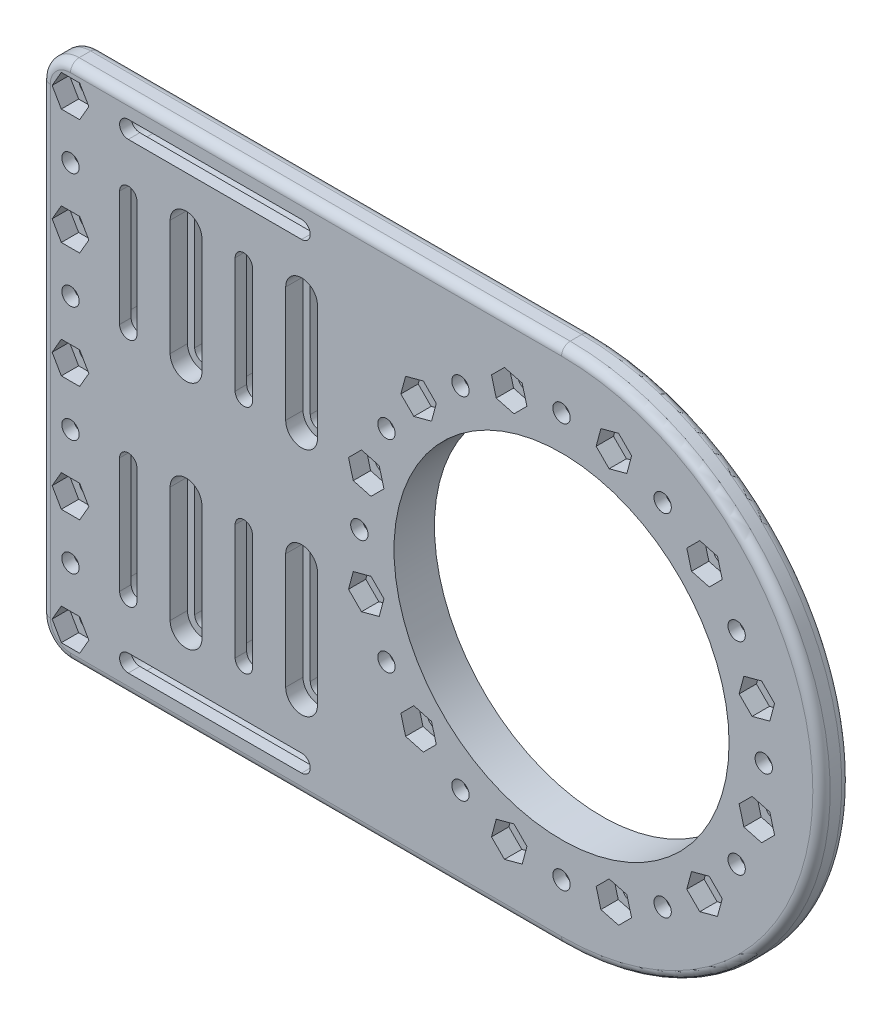
SolidWorks part; units mm, degrees
ref_plane "前视基准面" through (0, 0, 0) normal (0, 0, 1) x (1, 0, 0)
ref_plane "上视基准面" through (0, 0, 0) normal (0, 1, 0) x (1, 0, 0)
ref_plane "右视基准面" through (0, 0, 0) normal (1, 0, 0) x (0, 0, -1)
other "Configuration Table"
sketch "草图1" plane through (0, 0, 0) normal (0, 0, 1) x (1, 0, 0)
  line L1 (-45, -45) -> (45, -45)
  line L2 (-45, -45) -> (-45, 45)
  line L3 (-45, 45) -> (45, 45)
  line L4 (45, -45) -> (45, 45) construction
  line L5 (-45, -45) -> (45, 45) construction
  line L6 (-45, 45) -> (45, -45) construction
  arc A0 (45, -45) -> (45, 45) centre (45, 0) ccw
  point P0 (0, 0)
  dimension "D1" = 90
  dimension "D2" = 90
extrude "凸台-拉伸1" add sketch "草图1" along normal blind 5
sketch "草图2" plane through (0, 0, 5) normal (0, 0, 1) x (1, 0, 0)
  circle A0 centre (45, 0) radius 29
  dimension "D1" = 58
extrude "切除-拉伸1" cut sketch "草图2" against normal through all
sketch "草图3" plane through (0, 0, 0) normal (0, 0, 1) x (1, 0, 0)
  circle A0 centre (45, 0) radius 29
  circle A1 centre (45, 0) radius 45
  circle A2 centre (45, 0) radius 29 construction
  dimension "D1" = 90
extrude "凸台-拉伸2" add sketch "草图3" against normal blind 2
sketch "草图9" plane through (0, 0, -2) normal (0, 0, -1) x (-1, 0, 0)
  circle A0 centre (-45, 0) radius 45
  circle A1 centre (-45, 0) radius 31
  dimension "D1" = 62
extrude "切除-拉伸10" cut sketch "草图9" against normal blind 2
sketch "草图5" plane through (0, 0, 0) normal (0, 0, -1) x (-1, 0, 0)
  line L1 (-45, 35) -> (-45, 0) construction
  circle A0 centre (-45, 0) radius 35 construction
  circle A1 centre (-45, 35) radius 1.5
  dimension "D1" = 3
  dimension "D2" = 70
extrude "切除-拉伸2" cut sketch "草图5" against normal through all
sketch "草图6" plane through (0, 0, 0) normal (0, 0, -1) x (-1, 0, 0)
  line L0 (-45, 35) -> (-45, 0) construction
  line L1 (-45, 31.8246) -> (-42.25, 33.4123)
  line L2 (-42.25, 33.4123) -> (-42.25, 36.5877)
  line L3 (-42.25, 36.5877) -> (-45, 38.1754)
  line L4 (-45, 38.1754) -> (-47.75, 36.5877)
  line L5 (-47.75, 36.5877) -> (-47.75, 33.4123)
  line L6 (-47.75, 33.4123) -> (-45, 31.8246)
  circle A1 centre (-45, 35) radius 2.75 construction
  dimension "D1" = 5.5
extrude "切除-拉伸3" cut sketch "草图6" against normal blind 3
sketch "草图10" plane through (0, 0, -2) normal (0, 0, -1) x (-1, 0, 0)
  line L0 (-45, 0) -> (-35.9413, 33.8074) construction
  line L1 (-45, -1000) -> (-45, 49000) construction
  circle A0 centre (-35.9413, 33.8074) radius 1.5
  circle A1 centre (-45, 0) radius 35 construction
  dimension "D1" = 3
  dimension "D2" = 15
extrude "切除-拉伸11" cut sketch "草图10" against normal through all
sketch "草图11" plane through (0, 0, 5) normal (0, 0, 1) x (1, 0, 0)
  line L0 (35.9413, 33.8074) -> (45, 0) construction
  line L1 (36.7632, 30.7402) -> (39.0086, 32.9855)
  line L2 (39.0086, 32.9855) -> (38.1867, 36.0528)
  line L3 (38.1867, 36.0528) -> (35.1195, 36.8746)
  line L4 (35.1195, 36.8746) -> (32.8741, 34.6293)
  line L5 (32.8741, 34.6293) -> (33.696, 31.562)
  line L6 (33.696, 31.562) -> (36.7632, 30.7402)
  circle A0 centre (35.9413, 33.8074) radius 2.75 construction
  dimension "D1" = 5.5
extrude "切除-拉伸12" cut sketch "草图11" against normal blind 3
pattern_circular "阵列(圆周)1" count 12 over 360 about axis through (45, 0, 0) along (0, 0, 1) of "切除-拉伸3", "切除-拉伸2", "切除-拉伸11", "切除-拉伸12", "切除-拉伸1"
sketch "草图7" plane through (0, 0, 5) normal (0, 0, 1) x (1, 0, 0)
  line L0 (-30, 40) -> (0, 40) construction
  line L1 (-30, 41.5) -> (0, 41.5)
  line L2 (-30, 38.5) -> (0, 38.5)
  line L3 (-1000, 0) -> (49000, 0) construction
  line L4 (-30, -40) -> (0, -40) construction
  line L7 (-30, -41.5) -> (0, -41.5)
  line L8 (-30, -38.5) -> (0, -38.5)
  line L9 (-45, 45) -> (-45, -45) construction
  arc A0 (-30, 41.5) -> (-30, 38.5) centre (-30, 40) ccw
  arc A1 (0, 38.5) -> (0, 41.5) centre (0, 40) ccw
  arc A4 (-30, -41.5) -> (-30, -38.5) centre (-30, -40) cw
  arc A5 (0, -38.5) -> (0, -41.5) centre (0, -40) cw
  point P2 (-15, 40)
  point P12 (-15, -40)
  dimension "D1" = 3
  dimension "D2" = 80
  dimension "D3" = 15
  dimension "D4" = 30
sketch "草图8" plane through (0, 0, 0) normal (0, 0, 1) x (1, 0, 0)
  line L0 (-30, 40) -> (0, 40) construction
  line L1 (-30, 42.75) -> (0, 42.75)
  line L2 (-30, 37.25) -> (0, 37.25)
  line L3 (-30, -40) -> (0, -40) construction
  line L4 (-30, -37.25) -> (0, -37.25)
  line L5 (-30, -42.75) -> (0, -42.75)
  arc A0 (-30, 42.75) -> (-30, 37.25) centre (-30, 40) ccw
  arc A1 (0, 37.25) -> (0, 42.75) centre (0, 40) ccw
  arc A2 (-30, -37.25) -> (-30, -42.75) centre (-30, -40) ccw
  arc A3 (0, -42.75) -> (0, -37.25) centre (0, -40) ccw
  point P4 (-15, 40)
  point P13 (-15, -40)
  dimension "D1" = 5.5
  dimension "D2" = 5.5
extrude "切除-拉伸7" cut sketch "草图7" against normal through all
extrude "切除-拉伸9" cut sketch "草图8" along normal blind 3
sketch "草图12" plane through (0, 0, 5) normal (0, 0, 1) x (1, 0, 0)
  line L0 (-45, 45) -> (-45, -45) construction
  circle A0 centre (-40, 0) radius 1.5
  dimension "D2" = 3
  dimension "D1" = 5
sketch "草图13" plane through (0, 0, 5) normal (0, 0, 1) x (1, 0, 0)
  line L1 (-36.8246, 0) -> (-38.4123, 2.75)
  line L2 (-38.4123, 2.75) -> (-41.5877, 2.75)
  line L3 (-41.5877, 2.75) -> (-43.1754, 0)
  line L4 (-43.1754, 0) -> (-41.5877, -2.75)
  line L5 (-41.5877, -2.75) -> (-38.4123, -2.75)
  line L6 (-38.4123, -2.75) -> (-36.8246, 0)
  circle A1 centre (-40, 0) radius 2.75 construction
  dimension "D1" = 5.5
extrude "切除-拉伸13" cut sketch "草图12" against normal through all
extrude "切除-拉伸14" cut sketch "草图13" against normal blind 3
pattern_linear "阵列(线性)5" count 5 spacing 10 along (0, -1, 0) count 5 spacing 10 along (0, 1, 0) of "切除-拉伸13"
pattern_linear "阵列(线性)1" count 3 spacing 20 along (0, -1, 0) count 3 spacing 20 along (0, 1, 0) of "切除-拉伸14"
sketch "草图14" plane through (0, 0, 5) normal (0, 0, 1) x (1, 0, 0)
  line L0 (0, 30) -> (0, 10) construction
  line L1 (1.5, 30) -> (1.5, 10)
  line L2 (-1.5, 30) -> (-1.5, 10)
  line L3 (-1000, 0) -> (49000, 0) construction
  line L4 (0, -30) -> (0, -10) construction
  line L5 (1.5, -30) -> (1.5, -10)
  line L6 (-1.5, -30) -> (-1.5, -10)
  arc A0 (1.5, 30) -> (-1.5, 30) centre (0, 30) ccw
  arc A1 (-1.5, 10) -> (1.5, 10) centre (0, 10) ccw
  arc A2 (1.5, -30) -> (-1.5, -30) centre (0, -30) cw
  arc A3 (-1.5, -10) -> (1.5, -10) centre (0, -10) cw
  circle A4 centre (45, 0) radius 45 construction
  point P2 (0, 20)
  point P12 (0, -20)
  dimension "D1" = 3
  dimension "D2" = 30
  dimension "D3" = 20
  dimension "D4" = 0
sketch "草图15" plane through (0, 0, 5) normal (0, 0, 1) x (1, 0, 0)
  line L0 (0, 10) -> (0, 30) construction
  line L1 (-2.75, 10) -> (-2.75, 30)
  line L2 (2.75, 10) -> (2.75, 30)
  line L3 (0, -10) -> (0, -30) construction
  line L4 (2.75, -10) -> (2.75, -30)
  line L5 (-2.75, -10) -> (-2.75, -30)
  arc A0 (-2.75, 10) -> (2.75, 10) centre (0, 10) ccw
  arc A1 (2.75, 30) -> (-2.75, 30) centre (0, 30) ccw
  arc A2 (2.75, -10) -> (-2.75, -10) centre (0, -10) ccw
  arc A3 (-2.75, -30) -> (2.75, -30) centre (0, -30) ccw
  point P4 (0, 20)
  point P9 (0, -20)
  dimension "D1" = 5.5
  dimension "D2" = 5.5
sketch "草图17" plane through (0, 0, 0) normal (0, 0, -1) x (-1, 0, 0)
  line L1 (43.1754, 10) -> (41.5877, 12.75)
  line L2 (41.5877, 12.75) -> (38.4123, 12.75)
  line L3 (38.4123, 12.75) -> (36.8246, 10)
  line L4 (36.8246, 10) -> (38.4123, 7.25)
  line L5 (38.4123, 7.25) -> (41.5877, 7.25)
  line L6 (41.5877, 7.25) -> (43.1754, 10)
  circle A0 centre (40, 10) radius 2.75 construction
  dimension "D1" = 5.5
extrude "切除-拉伸18" cut sketch "草图17" against normal blind 3
pattern_linear "阵列(线性)6" count 3 spacing 20 along (0, -1, 0) count 3 spacing 20 along (0, 1, 0) of "切除-拉伸18"
extrude "切除-拉伸15" cut sketch "草图14" against normal through all
extrude "切除-拉伸16" cut sketch "草图15" against normal blind 3
pattern_linear "阵列(线性)2" count 4 spacing 10 along (-1, 0, 0) of "切除-拉伸15"
pattern_linear "阵列(线性)3" count 2 spacing 20 along (-1, 0, 0) of "切除-拉伸16"
sketch "草图16" plane through (0, 0, 0) normal (0, 0, -1) x (-1, 0, 0)
  line L0 (30, 30) -> (30, 10) construction
  line L3 (32.75, 30) -> (32.75, 10)
  line L6 (27.25, 30) -> (27.25, 10)
  line L7 (30, -10) -> (30, -30) construction
  line L8 (32.75, -10) -> (32.75, -30)
  line L9 (27.25, -10) -> (27.25, -30)
  arc A4 (32.75, 30) -> (27.25, 30) centre (30, 30) ccw
  arc A5 (27.25, 10) -> (32.75, 10) centre (30, 10) ccw
  arc A6 (32.75, -10) -> (27.25, -10) centre (30, -10) ccw
  arc A7 (27.25, -30) -> (32.75, -30) centre (30, -30) ccw
  point P4 (30, 20)
  point P9 (30, -20)
  dimension "D1" = 5.5
  dimension "D2" = 5.5
extrude "切除-拉伸17" cut sketch "草图16" against normal blind 3
pattern_linear "阵列(线性)4" count 2 spacing 20 along (1, 0, 0) of "切除-拉伸17"
fillet "圆角4" radius 1.5 8 edges at (0, -45, 5) (0, -45, 0) (90, 0, 0) (0, 45, 5) (0, 45, 0) (90, 0, 5) (-45, 0, 5) (-45, 0, 0)
fillet "圆角5" radius 5 6 edges at (-44.5607, -44.5607, 0.4393) (-44.5607, -44.5607, 4.5607) (-44.5607, 44.5607, 0.4393) (-44.5607, 44.5607, 4.5607) (-45, 45, 2.5) (-45, -45, 2.5)
